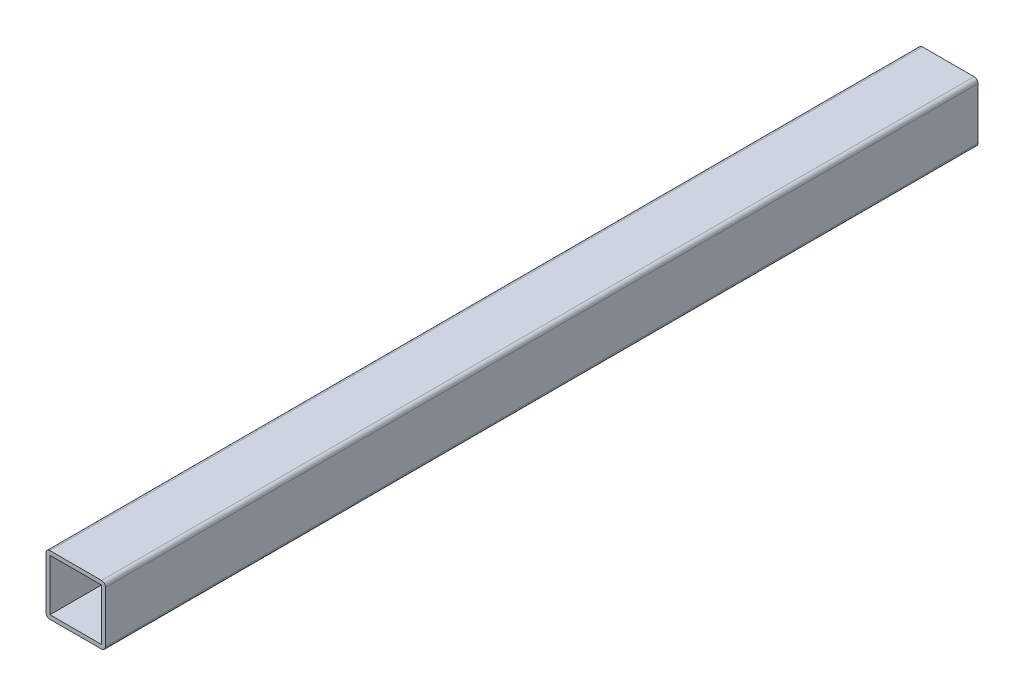
SolidWorks part; units mm, degrees
material "1.4003 (X2CrNi12)"
ref_plane "Ön Düzlem" through (0, 0, 0) normal (0, 0, 1) x (1, 0, 0)
ref_plane "Üst Düzlem" through (0, 0, 0) normal (0, 1, 0) x (1, 0, 0)
ref_plane "Sağ Düzlem" through (0, 0, 0) normal (1, 0, 0) x (0, 0, -1)
sketch "Çizim1" plane through (0, 0, 0) normal (0, 0, 1) x (1, 0, 0)
  line L0 (-13, -13) -> (13, -13)
  line L1 (-13, 15) -> (13, 15)
  line L2 (-15, 13) -> (-15, -13)
  line L3 (-13, -15) -> (13, -15)
  line L4 (15, 13) -> (15, -13)
  line L5 (-15, 15) -> (15, -15) construction
  line L6 (-15, -15) -> (15, 15) construction
  line L7 (13, 13) -> (13, -13)
  line L8 (-13, 13) -> (13, 13)
  line L9 (-13, 13) -> (-13, -13)
  line L10 (15, 15) -> (15, -15) construction
  line L11 (-15, -15) -> (15, -15) construction
  line L12 (-15, 15) -> (-15, -15) construction
  line L13 (-15, 15) -> (15, 15) construction
  arc A0 (15, -13) -> (13, -15) centre (13, -13) cw
  arc A1 (-15, -13) -> (-13, -15) centre (-13, -13) ccw
  arc A2 (13, 15) -> (15, 13) centre (13, 13) cw
  arc A3 (-13, 15) -> (-15, 13) centre (-13, 13) ccw
  point P0 (0, 0)
  dimension "D4" = 2
  dimension "D1" = 30
  dimension "D2" = 30
  dimension "D3" = 2
extrude "Yükseklik-Ekstrüzyon1" add sketch "Çizim1" along normal blind 220 and the other way blind 220
